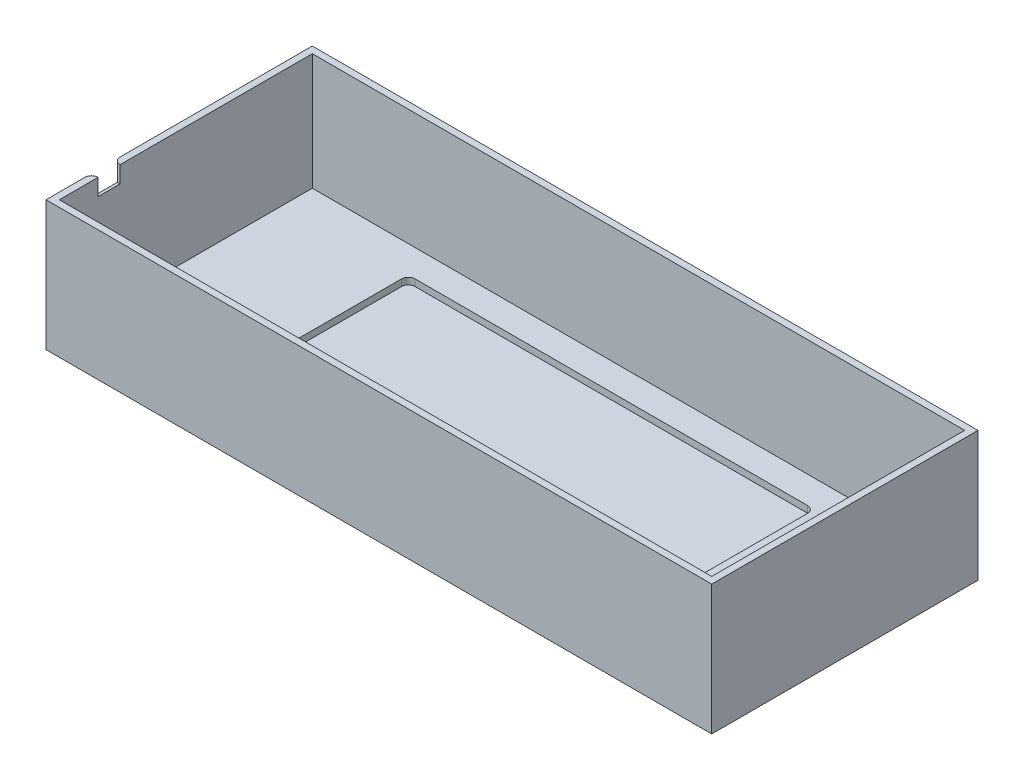
SolidWorks part; units mm, degrees
ref_plane "Front Plane" through (0, 0, 0) normal (0, 0, 1) x (1, 0, 0)
ref_plane "Top Plane" through (0, 0, 0) normal (0, 1, 0) x (1, 0, 0)
ref_plane "Right Plane" through (0, 0, 0) normal (1, 0, 0) x (0, 0, -1)
sketch "Sketch2" plane through (0, 0, 0) normal (0, 1, 0) x (1, 0, 0)
  line L1 (100, 40) -> (-100, 40)
  line L2 (100, 40) -> (100, -40)
  line L3 (100, -40) -> (-100, -40)
  line L4 (-100, 40) -> (-100, -40)
  line L5 (100, 40) -> (-100, -40) construction
  line L6 (100, -40) -> (-100, 40) construction
  point P0 (0, 0)
  dimension "D1" = 200
  dimension "D2" = 80
extrude "Boss-Extrude3" add sketch "Sketch2" along normal blind 37
shell "Shell2" thickness 2 removed face at (0, 37, 0)
sketch "Sketch3" plane through (0, 2, 0) normal (0, 1, 0) x (1, 0, 0)
  line L1 (61, 29.845) -> (-61, 29.845)
  line L2 (61, 29.845) -> (61, -29.845)
  line L3 (61, -29.845) -> (-61, -29.845)
  line L4 (-61, 29.845) -> (-61, -29.845)
  line L5 (61, 29.845) -> (-61, -29.845) construction
  line L6 (61, -29.845) -> (-61, 29.845) construction
  point P0 (0, 0)
  dimension "D1" = 122
  dimension "D2" = 59.69
extrude "Cut-Extrude1" cut sketch "Sketch3" against normal blind 2
sketch "Sketch4" plane through (0, 0, 0) normal (0, -1, 0) x (1, 0, 0)
  line L1 (-100, 40) -> (100, 40)
  line L2 (-100, 40) -> (-100, -40)
  line L3 (-100, -40) -> (100, -40)
  line L4 (100, 40) -> (100, -40)
extrude "Boss-Extrude4" add sketch "Sketch4" along normal blind 2
fillet "Fillet5" radius 2 4 edges at (61, 1, 29.845) (61, 1, -29.845) (-61, 1, 29.845) (-61, 1, -29.845)
sketch "Sketch5" plane through (0, 0, 0) normal (0, 1, 0) x (1, 0, 0)
  line L0 (-61, 0) -> (-36.56, 0) construction
  line L1 (-61, 27.845) -> (-61, -27.845) construction
sketch "Sketch6" plane through (0, 2, 0) normal (0, 1, 0) x (1, 0, 0)
  line L1 (-98, 38) -> (98, 38)
  line L2 (-98, 38) -> (-98, -38)
  line L3 (-98, -38) -> (98, -38)
  line L4 (98, 38) -> (98, -38)
  dimension "D1" = 196
  dimension "D2" = 76
sketch "Sketch7" plane through (-100, 0, 0) normal (-1, 0, 0) x (0, 0, 1)
  line L0 (40, 37) -> (26.33, 37) construction
  line L1 (-40, 37) -> (40, 37) construction
  line L3 (26.33, 37) -> (19.7545, 37)
  line L4 (26.33, 37) -> (26.33, 32)
  line L5 (26.33, 32) -> (19.7545, 32)
  line L6 (19.7545, 37) -> (19.7545, 32)
  dimension "D1" = 5
extrude "Cut-Extrude2" cut sketch "Sketch7" against normal blind 5
fillet "Fillet6" radius 2 3 edges at (-100, 34.5, 26.33) (-100, 34.5, 19.7545) (-100, 32, 23.0422)
